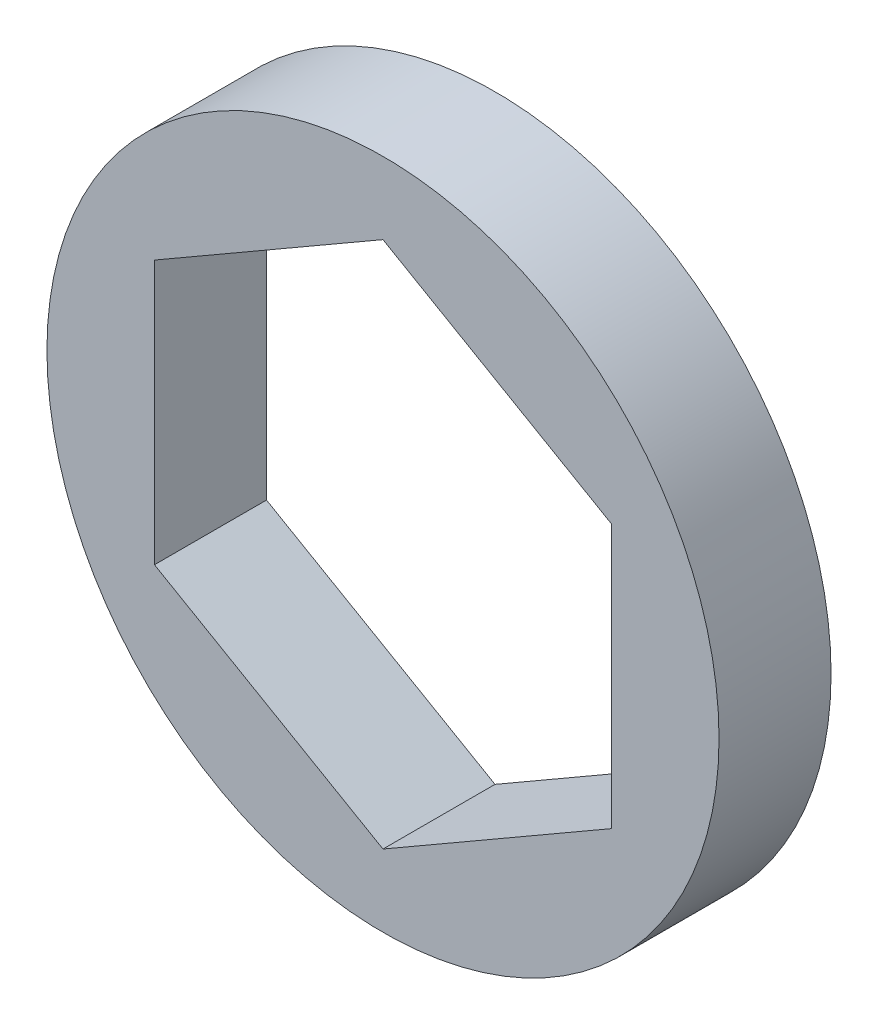
SolidWorks part; units mm, degrees
material "PET"
ref_plane "Front Plane" through (0, 0, 0) normal (0, 0, 1) x (1, 0, 0)
ref_plane "Top Plane" through (0, 0, 0) normal (0, 1, 0) x (1, 0, 0)
ref_plane "Right Plane" through (0, 0, 0) normal (1, 0, 0) x (0, 0, -1)
sketch "Sketch1" plane through (0, 0, 0) normal (0, 0, 1) x (1, 0, 0)
  line L1 (0, 7.479) -> (-6.477, 3.7395)
  line L2 (-6.477, 3.7395) -> (-6.477, -3.7395)
  line L3 (-6.477, -3.7395) -> (0, -7.479)
  line L4 (0, -7.479) -> (6.477, -3.7395)
  line L5 (6.477, -3.7395) -> (6.477, 3.7395)
  line L6 (6.477, 3.7395) -> (0, 7.479)
  circle A0 centre (0, 0) radius 9.525
  circle A1 centre (0, 0) radius 6.477 construction
  dimension "D1" = 12.954
  dimension "D2" = 19.05
extrude "Boss-Extrude1" add sketch "Sketch1" along normal mid plane 3.175
